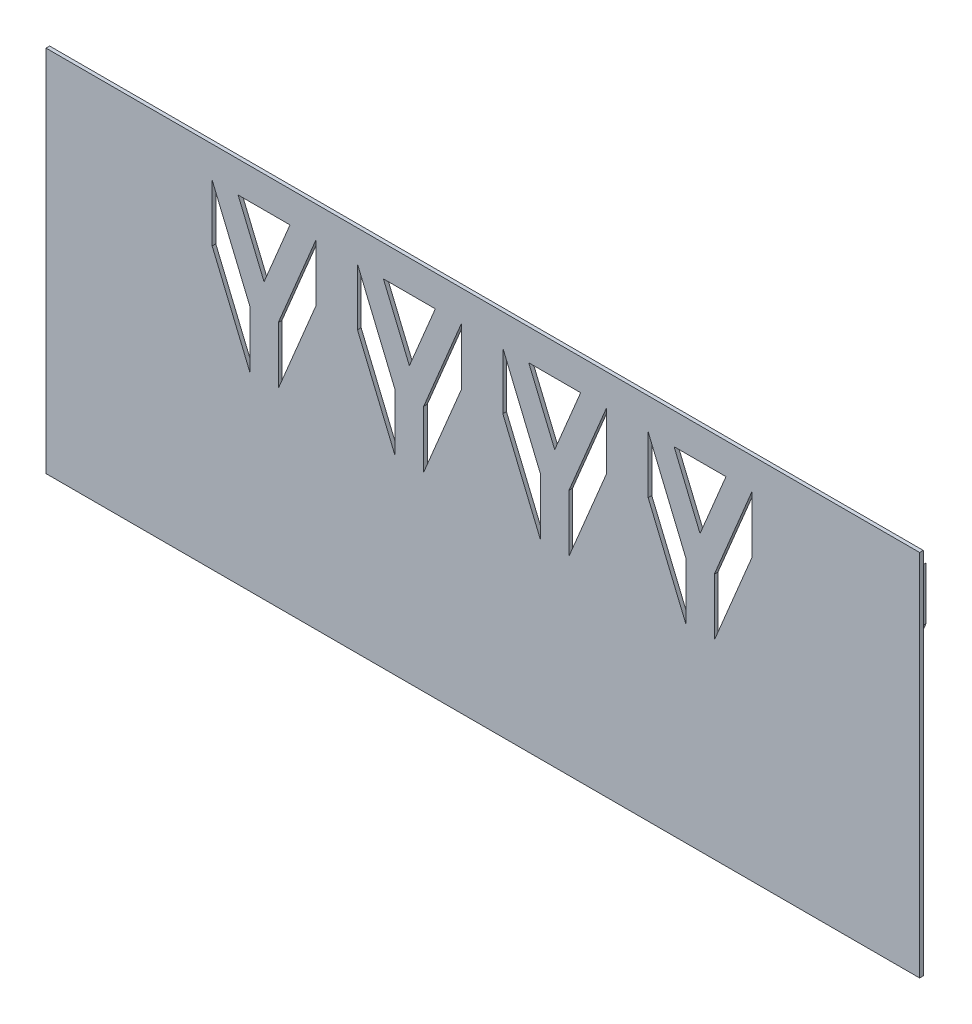
SolidWorks part; units mm, degrees
ref_plane "Front Plane" through (0, 0, 0) normal (0, 0, 1) x (1, 0, 0)
ref_plane "Top Plane" through (0, 0, 0) normal (0, 1, 0) x (1, 0, 0)
ref_plane "Right Plane" through (0, 0, 0) normal (1, 0, 0) x (0, 0, -1)
sketch "Sketch2" plane through (0, 0, 0) normal (0, 0, 1) x (1, 0, 0)
  line L1 (0, 0) -> (168.3109, 0)
  line L2 (0, 0) -> (0, -71)
  line L3 (0, -71) -> (168.3109, -71)
  line L4 (168.3109, 0) -> (168.3109, -71)
  line L30 (24.0048, -11.5) -> (32.0048, -11.5)
  line L52 (149.2598, -6.17) -> (154.0048, -17.558)
  line L65 (154.0048, -17.558) -> (158.7498, -6.17)
  line L75 (149.2598, -6.17) -> (158.7498, -6.17)
  line L84 (151.0848, -33.55) -> (151.0848, -23.434)
  line L96 (9.0048, -6) -> (19.0048, -6)
  line L97 (9.0048, -6) -> (14.0048, -18)
  line L98 (14.0048, -18) -> (19.0048, -6)
  line L99 (4.0048, -6) -> (4.0048, -17)
  line L100 (4.0048, -17) -> (11.2548, -34.4)
  line L101 (11.2548, -34.4) -> (11.2548, -23.4)
  line L102 (11.2548, -23.4) -> (4.0048, -6)
  line L103 (24.0048, -6) -> (24.0048, -17)
  line L104 (24.0048, -17) -> (16.7548, -34.4)
  line L105 (16.7548, -34.4) -> (16.7548, -23.4)
  line L106 (16.7548, -23.4) -> (24.0048, -6)
  line L109 (39.2548, -34.4) -> (39.2548, -23.4)
  line L110 (52.0048, -17) -> (44.7548, -34.4)
  line L111 (39.2548, -23.4) -> (32.0048, -6)
  line L112 (32.0048, -6) -> (32.0048, -17)
  line L113 (32.0048, -17) -> (39.2548, -34.4)
  line L114 (44.7548, -34.4) -> (44.7548, -23.4)
  line L115 (37.0048, -6) -> (42.0048, -18)
  line L116 (44.7548, -23.4) -> (52.0048, -6)
  line L117 (37.0048, -6) -> (47.0048, -6)
  line L118 (42.0048, -18) -> (47.0048, -6)
  line L119 (52.0048, -6) -> (52.0048, -17)
  line L123 (93.0048, -6) -> (103.0048, -6)
  line L124 (72.7548, -34.4) -> (72.7548, -23.4)
  line L126 (70.0048, -18) -> (75.0048, -6)
  line L127 (95.2548, -34.4) -> (95.2548, -23.4)
  line L128 (88.0048, -6) -> (88.0048, -17)
  line L129 (80.0048, -6) -> (80.0048, -17)
  line L130 (95.2548, -23.4) -> (88.0048, -6)
  line L131 (98.0048, -18) -> (103.0048, -6)
  line L132 (108.0048, -6) -> (108.0048, -17)
  line L133 (65.0048, -6) -> (70.0048, -18)
  line L134 (60.0048, -17) -> (67.2548, -34.4)
  line L135 (100.7548, -23.4) -> (108.0048, -6)
  line L138 (108.0048, -17) -> (100.7548, -34.4)
  line L139 (65.0048, -6) -> (75.0048, -6)
  line L141 (67.2548, -23.4) -> (60.0048, -6)
  line L142 (72.7548, -23.4) -> (80.0048, -6)
  line L143 (88.0048, -17) -> (95.2548, -34.4)
  line L144 (67.2548, -34.4) -> (67.2548, -23.4)
  line L145 (93.0048, -6) -> (98.0048, -18)
  line L146 (60.0048, -6) -> (60.0048, -17)
  line L147 (80.0048, -17) -> (72.7548, -34.4)
  line L148 (100.7548, -34.4) -> (100.7548, -23.4)
  line L149 (151.2548, -34.4) -> (151.2548, -23.4)
  line L150 (116.0048, -17) -> (123.2548, -34.4)
  line L151 (149.0048, -6) -> (154.0048, -18)
  line L152 (144.0048, -6) -> (144.0048, -17)
  line L153 (136.0048, -17) -> (128.7548, -34.4)
  line L154 (149.0048, -6) -> (159.0048, -6)
  line L155 (128.7548, -23.4) -> (136.0048, -6)
  line L156 (126.0048, -18) -> (131.0048, -6)
  line L157 (123.2548, -34.4) -> (123.2548, -23.4)
  line L158 (116.0048, -6) -> (116.0048, -17)
  line L159 (128.7548, -34.4) -> (128.7548, -23.4)
  line L160 (121.0048, -6) -> (126.0048, -18)
  line L161 (144.0048, -17) -> (151.2548, -34.4)
  line L162 (156.7548, -23.4) -> (164.0048, -6)
  line L163 (123.2548, -23.4) -> (116.0048, -6)
  line L164 (121.0048, -6) -> (131.0048, -6)
  line L165 (112, 0.1267) -> (116.0048, 0.1267)
  line L166 (154.0048, -18) -> (159.0048, -6)
  line L167 (136.0048, -6) -> (136.0048, -17)
  line L168 (151.2548, -23.4) -> (144.0048, -6)
  line L169 (156.7548, -34.4) -> (156.7548, -23.4)
  line L170 (151.0848, -23.434) -> (144.1748, -6.85)
  line L171 (144.1748, -6.85) -> (144.1748, -16.966)
  line L172 (164.0048, -6) -> (164.0048, -17)
  line L173 (164.0048, -17) -> (156.7548, -34.4)
  line L174 (144.1748, -16.966) -> (151.0848, -33.55)
  line L175 (156.9248, -23.434) -> (163.8348, -6.85)
  line L176 (163.8348, -6.85) -> (163.8348, -16.966)
  line L177 (163.8348, -16.966) -> (156.9248, -33.55)
  line L178 (156.9248, -33.55) -> (156.9248, -23.434)
  line L179 (9.2598, -6.17) -> (18.7498, -6.17)
  line L180 (14.0048, -17.558) -> (18.7498, -6.17)
  line L181 (9.2598, -6.17) -> (14.0048, -17.558)
  line L182 (4.1748, -6.85) -> (4.1748, -16.966)
  line L183 (4.1748, -16.966) -> (11.0848, -33.55)
  line L184 (11.0848, -33.55) -> (11.0848, -23.434)
  line L185 (11.0848, -23.434) -> (4.1748, -6.85)
  line L186 (23.8348, -6.85) -> (23.8348, -16.966)
  line L187 (23.8348, -16.966) -> (16.9248, -33.55)
  line L188 (16.9248, -33.55) -> (16.9248, -23.434)
  line L189 (16.9248, -23.434) -> (23.8348, -6.85)
  point P23 (14.0048, -6)
  point P42 (42.0048, -6)
  point P59 (70.0048, -6)
  point P74 (98.0048, -6)
  point P88 (126.0048, -6)
  point P103 (154.0048, -6)
  dimension "D1" = 168.3109
  dimension "D2" = 71
  dimension "D3" = 0.17
  dimension "D4" = 10
  dimension "D5" = 11
  dimension "D6" = 10
  dimension "D7" = 11
  dimension "D8" = 10
  dimension "D9" = 11
  dimension "D10" = 10
  dimension "D11" = 11
  dimension "D12" = 10
  dimension "D13" = 11
  dimension "D14" = 10
  dimension "D15" = 11
extrude "Boss-Extrude3" add sketch "Sketch2" along normal blind 0.7 contours L4 L1 L2 L3 L168 L149 L161 L152 L166 L151 L154 L163 L157 L150 L158 L146 L141 L144 L134 L145 L123 L131 L143 L128 L130 L127 L118 L115 L117 L113 L112 L103 L104 L105 L106 L111 L109 L102 | L151 L166 L154 | L149 L168 L152 L161 | L173 L172 L162 L169 | L101 L102 L99 L100 | L97 L98 L96 | L106 L105 L104 L103 | L175 L176 L177 L178 | L52 L65 L75 | L84 L170 L171 L174 | L179 L180 L181 | L182 L183 L184 L185 | L186 L187 L188 L189 region at (84.1741, -37.7404, 0) region at (23.9755, -14.25, 0) region at (14.0048, -6.1562, 0) region at (7.6028, -14.7113, 0) region at (147.6569, -25.6887, 0) region at (154.0048, -6.1562, 0) region at (160.4069, -14.7113, 0)
extrude "Boss-Extrude5" add sketch "Sketch2<6>" against normal blind 5 contours L179 L181 L180 | L184 L185 L182 L183 | L189 L188 L187 L186 | L75 L52 L65 | L171 L174 L84 L170 | L178 L177 L176 L175 region at (154.0048, -9.966, 0) region at (147.6298, -20.2, 0) region at (160.3798, -20.2, 0) region at (14.0048, -9.966, 0) region at (7.6298, -20.2, 0) region at (20.3798, -20.2, 0)
sketch "Sketch2<6>" plane through (0, 0, 0) normal (0, 0, 1) x (1, 0, 0) same geometry as "Sketch2"
